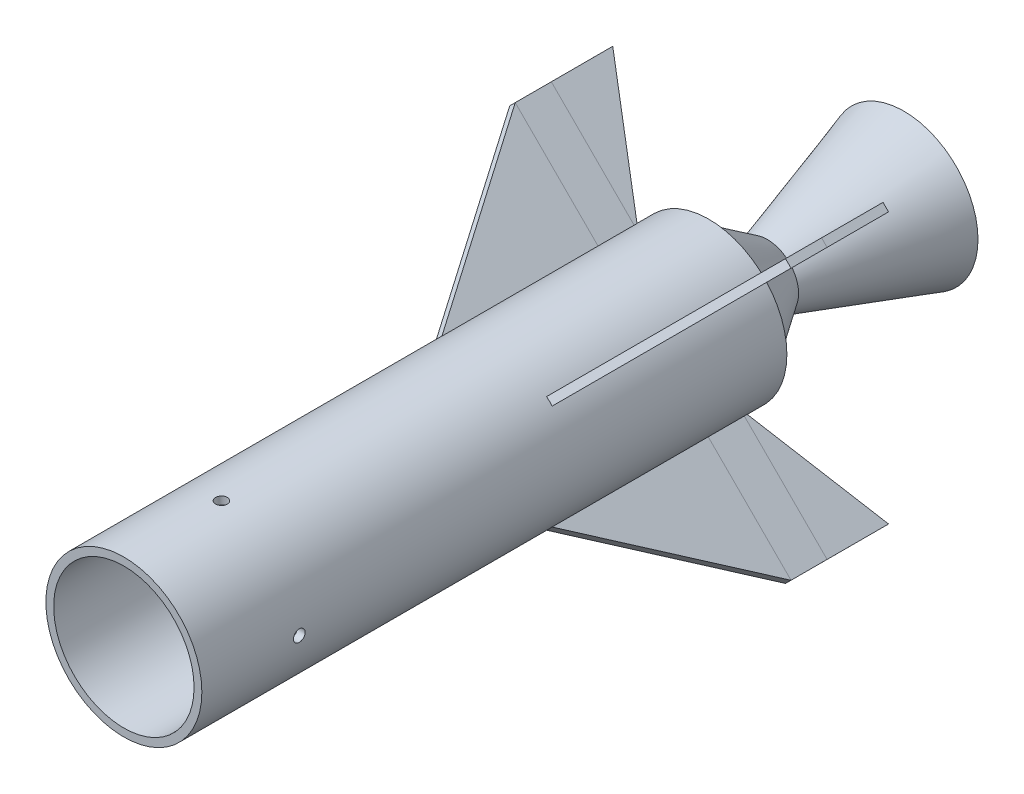
SolidWorks part; units mm, degrees
ref_plane "前视基准面" through (0, 0, 0) normal (0, 0, 1) x (1, 0, 0)
ref_plane "上视基准面" through (0, 0, 0) normal (0, 1, 0) x (1, 0, 0)
ref_plane "右视基准面" through (0, 0, 0) normal (1, 0, 0) x (0, 0, -1)
sketch "草图1" plane through (0, 0, 0) normal (0, 0, 1) x (1, 0, 0)
  circle A0 centre (0, 0) radius 40
extrude "凸台-拉伸1" add sketch "草图1" along normal blind 300
ref_plane "基准面1" through (0, 0, 8) normal (0, 0, 1) x (1, 0, 0)
sketch "草图2" plane through (0, 0, 8) normal (0, 0, 1) x (1, 0, 0)
  circle A0 centre (0, 0) radius 36
extrude "切除-拉伸1" cut sketch "草图2" along normal blind 292
ref_plane "基准面2" through (40, 0, 0) normal (1, 0, 0) x (0, 0, -1)
sketch "草图4" plane through (40, 0, 0) normal (1, 0, 0) x (0, 0, -1)
  circle A0 centre (-250, 0) radius 3
extrude "切除-拉伸2" cut sketch "草图4" against normal blind 5
ref_plane "基准面3" through (0, 40, 0) normal (0, 1, 0) x (1, 0, 0)
sketch "草图5" plane through (0, 40, 0) normal (0, 1, 0) x (1, 0, 0)
  circle A0 centre (0, -250) radius 3
extrude "切除-拉伸3" cut sketch "草图5" against normal blind 5
ref_plane "基准面4" through (-40, 0, 0) normal (1, 0, 0) x (0, 0, -1)
sketch "草图6" plane through (-40, 0, 0) normal (1, 0, 0) x (0, 0, -1)
  circle A0 centre (-250, 0) radius 3
extrude "切除-拉伸4" cut sketch "草图6" along normal blind 5
ref_plane "基准面5" through (0, -40, 0) normal (0, 1, 0) x (1, 0, 0)
sketch "草图7" plane through (0, -40, 0) normal (0, 1, 0) x (1, 0, 0)
  circle A0 centre (0, -250) radius 3
extrude "切除-拉伸5" cut sketch "草图7" along normal blind 5
ref_plane "基准面6" through (0, 0, -20) normal (0, 0, 1) x (1, 0, 0)
ref_plane "基准面7" through (0, 0, 11.5) normal (0, 0, 1) x (1, 0, 0)
ref_plane "基准面8" through (0, 0, 30) normal (0, 0, 1) x (1, 0, 0)
ref_plane "基准面9" through (0, 0, 114) normal (0, 0, 1) x (1, 0, 0)
ref_axis "基准轴1" through (0, 0, 320) along (0, 0, -1)
sketch "草图21" plane through (0, 0, 0) normal (0, 1, 0) x (1, 0, 0)
  line L0 (0, 0) -> (0, 1) construction
  line L1 (30, 0) -> (12, 30)
  line L2 (12, 30) -> (34, 100)
  line L3 (34, 100) -> (38, 100)
  line L4 (38, 100) -> (16, 30)
  line L5 (16, 30) -> (36, 0)
  line L6 (36, 0) -> (30, 0)
revolve "旋转3" add sketch "草图21" angle 360 about L0
sketch "草图41" plane through (0, 0, -20) normal (0, 0, 1) x (1, 0, 0)
  line L0 (69.2894, 72.1178) -> (69.3035, 72.1319)
  line L1 (69.3035, 72.1319) -> (72.1319, 69.3035)
  line L2 (72.1319, 69.3035) -> (72.1178, 69.2894)
  line L3 (72.1178, 69.2894) -> (69.2894, 72.1178)
sketch "草图42" plane through (0, 0, 11.5) normal (0, 0, 1) x (1, 0, 0)
  line L0 (24.7487, 27.5771) -> (69.2964, 72.1249)
  line L1 (69.2964, 72.1249) -> (72.1249, 69.2964)
  line L2 (72.1249, 69.2964) -> (27.5771, 24.7487)
  line L3 (27.5771, 24.7487) -> (24.7487, 27.5771)
loft "放样10" add profiles "草图41", "草图42"
pattern_circular "阵列(圆周)6" count 4 over 360 about axis through (0, 0, 320) along (0, 0, -1) of "放样10"
sketch "草图43" plane through (0, 0, 11.5) normal (0, 0, 1) x (1, 0, 0)
  line L0 (24.7487, 27.5771) -> (69.2964, 72.1249)
  line L1 (69.2964, 72.1249) -> (72.1249, 69.2964)
  line L2 (72.1249, 69.2964) -> (27.5771, 24.7487)
  line L3 (27.5771, 24.7487) -> (24.7487, 27.5771)
extrude "凸台-拉伸4" add sketch "草图43" along normal blind 18.5
pattern_circular "阵列(圆周)7" count 4 over 360 about axis through (0, 0, 320) along (0, 0, -1) of "凸台-拉伸4"
sketch "草图44" plane through (0, 0, 30) normal (0, 0, 1) x (1, 0, 0)
  line L0 (24.7487, 27.5771) -> (69.2964, 72.1249)
  line L1 (69.2964, 72.1249) -> (72.1249, 69.2964)
  line L2 (72.1249, 69.2964) -> (27.5771, 24.7487)
  line L3 (27.5771, 24.7487) -> (24.7487, 27.5771)
sketch "草图45" plane through (0, 0, 114) normal (0, 0, 1) x (1, 0, 0)
  line L0 (24.7421, 27.5705) -> (24.7565, 27.5849)
  line L1 (24.7565, 27.5849) -> (27.5849, 24.7565)
  line L2 (27.5849, 24.7565) -> (27.5705, 24.7421)
  line L3 (27.5705, 24.7421) -> (24.7421, 27.5705)
loft "放样11" add profiles "草图44", "草图45"
pattern_circular "阵列(圆周)8" count 4 over 360 about axis through (0, 0, 320) along (0, 0, -1) of "放样11"
sketch "草图46" plane through (0, 0, 0) normal (0, 0, 1) x (1, 0, 0)
  circle A0 centre (0, 0) radius 30
extrude "切除-拉伸7" cut sketch "草图46" along normal blind 8
